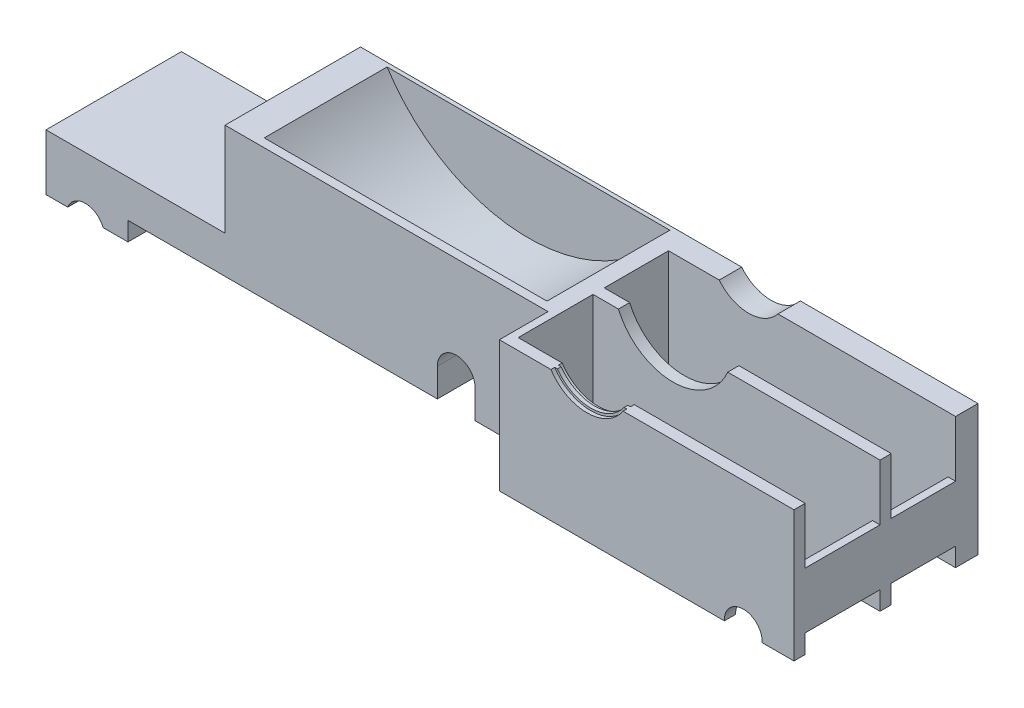
SolidWorks part; units mm, degrees
ref_plane "Front Plane" through (0, 0, 0) normal (0, 0, 1) x (1, 0, 0)
ref_plane "Top Plane" through (0, 0, 0) normal (0, 1, 0) x (1, 0, 0)
ref_plane "Right Plane" through (0, 0, 0) normal (1, 0, 0) x (0, 0, -1)
sketch "Sketch1" plane through (0, 0, 0) normal (0, 1, 0) x (1, 0, 0)
  line L1 (0, 0) -> (419.1, 0)
  line L2 (0, 0) -> (0, 142.1841)
  line L3 (0, 142.1841) -> (419.1, 142.1841)
  line L4 (419.1, 0) -> (419.1, 142.1841)
  dimension "D1" = 419.1
  dimension "D2" = 142.1841
extrude "Boss-Extrude1" add sketch "Sketch1" along normal blind 88.9
ref_plane "Plane1" through (0, 0, -134.333) normal (0, 0, -1) x (-1, 0, 0)
ref_plane "Plane2" through (0, 0, -67.8332) normal (0, 0, -1) x (-1, 0, 0)
ref_plane "Plane3" through (0, 0, -14.4831) normal (0, 0, -1) x (-1, 0, 0)
ref_plane "Plane4" through (0, 0, -131.633) normal (0, 0, -1) x (-1, 0, 0)
sketch "Sketch2" plane through (0, 0, -131.633) normal (0, 0, -1) x (-1, 0, 0)
  circle A0 centre (-116.7166, 150.0612) radius 119.38
  arc A1 (-20.1165, 209.6486) -> (-213.3168, 90.4738) centre (-116.7166, 150.0612) ccw construction
  dimension "D1" = 238.76
sketch "Sketch3" plane through (0, 0, -134.333) normal (0, 0, -1) x (-1, 0, 0)
  line L0 (-116.7166, 150.0612) -> (-278.6494, 104.852) construction
  circle A0 centre (-278.6494, 104.852) radius 24.9999
sketch "Sketch4" plane through (0, 0, -67.8332) normal (0, 0, -1) x (-1, 0, 0)
  circle A0 centre (-278.6494, 104.852) radius 40.386
  dimension "D1" = 80.772
sketch "Sketch5" plane through (0, 0, -14.4831) normal (0, 0, -1) x (-1, 0, 0)
  circle A0 centre (-278.6494, 104.852) radius 27.686
  dimension "D1" = 55.372
sketch "Sketch6" plane through (0, 88.9, 0) normal (0, 1, 0) x (1, 0, 0)
  line L0 (278.6494, 14.4831) -> (278.6494, 11.9431) construction
  line L1 (306.3354, 14.4831) -> (250.9634, 14.4831) construction
  line L2 (278.6494, 67.8332) -> (278.6494, 60.2336) construction
  line L3 (319.0354, 67.8332) -> (238.2634, 67.8332) construction
  line L4 (278.6494, 134.333) -> (278.6494, 119.093) construction
  line L5 (303.6493, 134.333) -> (253.6494, 134.333) construction
  dimension "D1" = 2.54
  dimension "D2" = 7.5997
  dimension "D3" = 15.24
extrude "Cut-Extrude1" cut sketch "Sketch2" against normal blind 83.4009
sketch "Sketch7" plane through (0, 88.9, 0) normal (0, 1, 0) x (1, 0, 0)
  line L0 (419.1, 0) -> (419.1, 142.1841) construction
  line L1 (419.1, 119.093) -> (224.3193, 119.093)
  line L2 (419.1, 119.093) -> (419.1, 75.4532)
  line L3 (419.1, 67.8332) -> (224.3193, 67.8332)
  line L4 (224.3193, 119.093) -> (224.3193, 75.4532)
  line L5 (319.0354, 67.8332) -> (238.2634, 67.8332) construction
  line L11 (219.2393, 131.633) -> (219.2393, 48.2321) construction
  line L12 (224.3193, 75.4532) -> (419.1, 75.4532)
  line L13 (419.1, 67.8332) -> (419.1, 17.0332)
  line L14 (224.3193, 67.8332) -> (224.3193, 17.0332)
  line L15 (224.3193, 17.0332) -> (419.1, 17.0332)
  dimension "D1" = 5.08
  dimension "D2" = 7.62
  dimension "D3" = 50.8
  dimension "D4" = 50.8
extrude "Cut-Extrude2" cut sketch "Sketch7" against normal through all
extrude "Cut-Extrude4" cut sketch "Sketch4" along normal blind 10
ref_axis "Axis1" through (278.6494, 104.852, -330.8365) along (0, 0, 1)
sketch "Sketch18" plane through (0, 0, -142.1841) normal (0, 0, -1) x (-1, 0, 0)
  circle A0 centre (-278.6494, 104.852) radius 25.527
  dimension "D1" = 51.054
extrude "Cut-Extrude11" cut sketch "Sketch18" against normal up to surface (23.0911 mm away) up to face at (321.7096, 44.45, -119.093)
extrude "Cut-Extrude5" cut sketch "Sketch5" against normal through all
sketch "Sketch8" plane through (0, 0, -142.1841) normal (0, 0, -1) x (-1, 0, 0)
  line L1 (-419.1, 88.9) -> (0, 88.9)
  line L2 (-419.1, 88.9) -> (-419.1, 0)
  line L3 (-419.1, 0) -> (0, 0)
  line L4 (0, 88.9) -> (0, 0)
extrude "Cut-Extrude6" cut sketch "Sketch8" against normal up to vertex (7.8511 mm away) up to point (278.6494, 88.9, -134.333)
sketch "Sketch9" plane through (0, 0, 0) normal (0, 0, 1) x (1, 0, 0)
  line L1 (0, 88.9) -> (419.1, 88.9)
  line L2 (0, 88.9) -> (0, 0)
  line L3 (0, 0) -> (419.1, 0)
  line L4 (419.1, 88.9) -> (419.1, 0)
extrude "Cut-Extrude7" cut sketch "Sketch9" against normal up to vertex (11.9431 mm away) up to point (278.6494, 88.9, -11.9431)
sketch "Sketch10" plane through (0, 0, -11.9431) normal (0, 0, 1) x (1, 0, 0)
  line L0 (0, 0) -> (419.1, 0) construction
  line L1 (0, 88.9) -> (219.202, 88.9)
  line L2 (0, 88.9) -> (0, 0)
  line L3 (0, 0) -> (219.202, 0)
  line L4 (219.202, 88.9) -> (219.202, 0)
  dimension "D1" = 219.202
extrude "Cut-Extrude8" cut sketch "Sketch10" against normal blind 30.48
sketch "Sketch12" plane through (0, 0, 0) normal (0, -1, 0) x (1, 0, 0)
  line L5 (0, -42.4231) -> (-121.5336, -42.4231)
  line L6 (0, -42.4231) -> (0, -134.333)
  line L7 (0, -134.333) -> (-121.5336, -134.333)
  line L8 (-121.5336, -42.4231) -> (-121.5336, -134.333)
  line L9 (0, -88.378) -> (53.0931, -88.378) construction
  line L10 (0, -134.333) -> (0, -42.4231) construction
  line L11 (0, -42.4231) -> (219.202, -42.4231) construction
  point P9 (0, -88.378)
  dimension "D1" = 121.5336
extrude "Boss-Extrude2" add sketch "Sketch12" against normal blind 25.4
sketch "Sketch14" plane through (0, 0, 0) normal (0, -1, 0) x (1, 0, 0)
  line L0 (419.1, -134.333) -> (-121.5336, -134.333) construction
  line L1 (-121.5336, -42.4231) -> (-65.8865, -42.4231)
  line L2 (-121.5336, -42.4231) -> (-121.5336, -134.333)
  line L3 (-121.5336, -134.333) -> (-65.8865, -134.333)
  line L4 (-65.8865, -42.4231) -> (-65.8865, -134.333)
extrude "Boss-Extrude3" add sketch "Sketch14" along normal blind 12.7
sketch "Sketch17" plane through (0, 0, -134.333) normal (0, 0, -1) x (-1, 0, 0)
  line L0 (-169.736, 19.3164) -> (-169.736, 0)
  line L1 (-419.1, 0) -> (65.8865, 0) construction
  line L2 (-169.736, 0) -> (-144.082, 0)
  line L3 (-144.082, 0) -> (-144.082, 19.3164)
  circle A0 centre (-384.7359, 0.5319) radius 12.827
  arc A1 (-144.082, 19.3164) -> (-169.736, 19.3164) centre (-156.909, 19.3164) ccw
  circle A2 centre (94.7989, -17.274) radius 12.827
  dimension "D1" = 25.654
  dimension "D2" = 25.654
  dimension "D3" = 25.654
extrude "Cut-Extrude10" cut sketch "Sketch17" against normal up to surface (122.3899 mm away) up to face at (305.6505, 57.311, -11.9431)
ref_plane "Plane5" through (219.202, 0, 0) normal (-1, 0, 0) x (0, 0, 1)
sketch "Sketch20" plane through (0, 0, -17.0332) normal (0, 0, -1) x (-1, 0, 0)
  line L0 (-419.1, 88.9) -> (-419.1, 0) construction
  line L1 (-419.1, 50.8) -> (-414.02, 50.8)
  line L2 (-419.1, 50.8) -> (-419.1, 12.7)
  line L3 (-419.1, 12.7) -> (-414.02, 12.7)
  line L4 (-414.02, 50.8) -> (-414.02, 12.7)
  line L5 (-419.1, 0) -> (-397.5519, 0) construction
  dimension "D1" = 12.7
  dimension "D2" = 38.1
  dimension "D3" = 5.08
extrude "Boss-Extrude4" add sketch "Sketch20" along normal up to surface (117.2997 mm away) up to face at (123.7872, 23.2831, -134.333)
sketch "Sketch22" plane through (0, 0, -11.9431) normal (0, 0, 1) x (1, 0, 0)
  line L1 (219.202, 0) -> (419.1, 0)
  line L2 (219.202, 0) -> (219.202, 88.9)
  line L3 (219.202, 88.9) -> (419.1, 88.9)
  line L4 (419.1, 0) -> (419.1, 88.9)
extrude "Boss-Extrude5" add sketch "Sketch22" along normal blind 2.54
sketch "Sketch24" plane through (0, 0, -9.4031) normal (0, 0, 1) x (1, 0, 0)
  circle A0 centre (278.6494, 104.852) radius 29.21
  circle A2 centre (278.6494, 104.852) radius 27.5 construction
  dimension "D1" = 58.42
extrude "Cut-Extrude12" cut sketch "Sketch24" against normal blind 2.54 contours A0
extrude "Cut-Extrude13" cut sketch "Sketch24<4>" along normal up to surface (-5.08 mm away) from surface up to face at (278.6494, 83.033, -14.4831) starting at face at (372.255, 31.8159, -17.0332)
sketch "Sketch24<4>" plane through (0, 0, -9.4031) normal (0, 0, 1) x (1, 0, 0) same geometry as "Sketch24"
sketch "Sketch29" plane through (0, 0, -11.9431) normal (0, 0, -1) x (-1, 0, 0)
  circle A4 centre (-384.7359, 0.5319) radius 12.827
  arc A5 (-371.92, 0) -> (-397.5519, 0) centre (-384.7359, 0.5319) ccw construction
extrude "Cut-Extrude14" cut sketch "Sketch29" against normal through all
sketch "Sketch30" plane through (0, 0, -134.333) normal (0, 0, -1) x (-1, 0, 0)
  line L0 (-14.194, 88.9) -> (-20.7587, 88.9)
  line L1 (0, 88.9) -> (-258.7205, 88.9) construction
  line L2 (-212.6746, 88.9) -> (-219.2393, 88.9)
  arc A0 (-219.2393, 88.9) -> (-14.194, 88.9) centre (-116.7166, 150.0612) ccw
  arc A1 (-219.2393, 88.9) -> (-14.194, 88.9) centre (-116.7166, 150.0612) ccw construction
  arc A2 (-212.6746, 88.9) -> (-20.7587, 88.9) centre (-116.7166, 150.0612) ccw
  dimension "D1" = 227.584
extrude "Boss-Extrude6" add sketch "Sketch30" against normal up to surface (86.1009 mm away) contours A2 L0 A0 L2 up to face at (116.7166, 59.7906, -48.2321)
